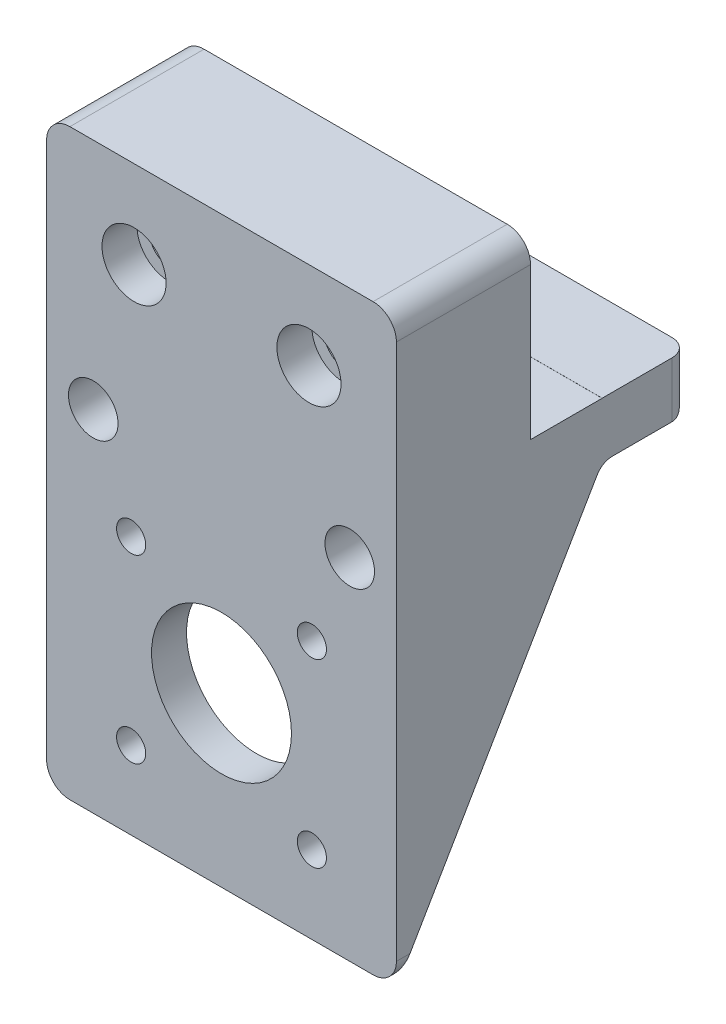
SolidWorks part; units mm, degrees
ref_plane "Front Plane" through (0, 0, 0) normal (0, 0, 1) x (1, 0, 0)
ref_plane "Top Plane" through (0, 0, 0) normal (0, 1, 0) x (1, 0, 0)
ref_plane "Right Plane" through (0, 0, 0) normal (1, 0, 0) x (0, 0, -1)
ref_plane "Plano1" through (0, 0, 29.3) normal (0, 0, 1) x (1, 0, 0)
sketch "Esboço1" plane through (0, 0, 29.3) normal (0, 0, 1) x (1, 0, 0)
  line L0 (-219.9808, -83.15) -> (-219.9808, -59.15) construction
  line L1 (-219.9808, -100) -> (-219.9808, 0) construction
  line L7 (-245.9808, -100) -> (-193.9808, -100)
  line L8 (-249.9808, -96) -> (-249.9808, -4)
  line L9 (-245.9808, 0) -> (-193.9808, 0)
  line L10 (-189.9808, -96) -> (-189.9808, -4)
  arc A0 (-193.9808, 0) -> (-189.9808, -4) centre (-193.9808, -4) cw
  arc A1 (-249.9808, -4) -> (-245.9808, 0) centre (-245.9808, -4) cw
  circle A3 centre (-219.9808, -71.15) radius 12
  arc A4 (-193.9808, -100) -> (-189.9808, -96) centre (-193.9808, -96) ccw
  circle A6 centre (-235.4808, -86.65) radius 2.5
  arc A7 (-245.9808, -100) -> (-249.9808, -96) centre (-245.9808, -96) cw
  circle A9 centre (-235.4808, -55.65) radius 2.5
  circle A12 centre (-204.4808, -86.65) radius 2.5
  circle A15 centre (-204.4808, -55.65) radius 2.5
  point P28 (-189.9808, 0)
  point P31 (-249.9808, 0)
  point P36 (-249.9808, -100)
  dimension "D8" = 4
  dimension "D6" = 100
  dimension "D7" = 60
extrude "Ressalto-extrusão1" add sketch "Esboço1" along normal blind 6
sketch "Esboço2" plane through (0, 0, 29.3) normal (0, 0, -1) x (-1, 0, 0)
  line L8 (189.9808, -4) -> (189.9808, -96)
  line L9 (193.9808, -100) -> (245.9808, -100)
  line L10 (249.9808, -96) -> (249.9808, -4)
  line L11 (245.9808, 0) -> (193.9808, 0)
  line L12 (189.9808, -4) -> (189.9808, -96)
  line L13 (193.9808, -100) -> (245.9808, -100)
  line L14 (249.9808, -96) -> (249.9808, -4)
  line L15 (245.9808, 0) -> (193.9808, 0)
  line L28 (237.9592, -48) -> (202.0024, -48)
  line L29 (202.0024, -48) -> (196.8308, -53.1716)
  line L30 (196.8308, -53.1716) -> (196.8308, -89.1284)
  line L31 (196.8308, -89.1284) -> (202.0024, -94.3)
  line L32 (202.0024, -94.3) -> (237.9592, -94.3)
  line L33 (237.9592, -94.3) -> (243.1308, -89.1284)
  line L34 (243.1308, -89.1284) -> (243.1308, -53.1716)
  line L35 (243.1308, -53.1716) -> (237.9592, -48)
  line L36 (237.9592, -48) -> (202.0024, -48)
  line L37 (202.0024, -48) -> (196.8308, -53.1716)
  line L38 (196.8308, -53.1716) -> (196.8308, -89.1284)
  line L39 (196.8308, -89.1284) -> (202.0024, -94.3)
  line L40 (202.0024, -94.3) -> (237.9592, -94.3)
  line L41 (237.9592, -94.3) -> (243.1308, -89.1284)
  line L42 (243.1308, -89.1284) -> (243.1308, -53.1716)
  line L43 (243.1308, -53.1716) -> (237.9592, -48)
  arc A8 (193.9808, 0) -> (189.9808, -4) centre (193.9808, -4) ccw
  arc A9 (189.9808, -96) -> (193.9808, -100) centre (193.9808, -96) ccw
  arc A10 (245.9808, -100) -> (249.9808, -96) centre (245.9808, -96) ccw
  arc A11 (249.9808, -4) -> (245.9808, 0) centre (245.9808, -4) ccw
  arc A12 (193.9808, 0) -> (189.9808, -4) centre (193.9808, -4) ccw
  arc A13 (189.9808, -96) -> (193.9808, -100) centre (193.9808, -96) ccw
  arc A14 (245.9808, -100) -> (249.9808, -96) centre (245.9808, -96) ccw
  arc A15 (249.9808, -4) -> (245.9808, 0) centre (245.9808, -4) ccw
  dimension "D1" = 0
  dimension "D2" = 3
extrude "Ressalto-extrusão2" add sketch "Esboço2" along normal blind 50
sketch "Esboço3" plane through (-249.9808, 0, 0) normal (-1, 0, 0) x (0, 0, 1)
  line L2 (35.3, -100) -> (-20.7, -100)
  line L3 (35.3, -100) -> (-20.7, -100)
  line L20 (35.3, -100) -> (0, -39.4857)
  line L21 (-20.7, -31.0564) -> (-20.7, -100)
  line L22 (0, -39.4857) -> (0, -31.0564)
  line L26 (0, -31.0564) -> (-20.7, -31.0564)
  dimension "D1" = 0
extrude "Corte-extrusão1" cut sketch "Esboço3" against normal through all
sketch "Esboço4" plane through (0, 0, 0) normal (0, 0, -1) x (-1, 0, 0)
  line L1 (189.9808, -39.4857) -> (249.9808, -39.4857)
  line L2 (189.9808, -39.4857) -> (189.9808, -29.9857)
  line L3 (189.9808, -29.9857) -> (249.9808, -29.9857)
  line L4 (249.9808, -39.4857) -> (249.9808, -29.9857)
  dimension "D1" = 9.5
sketch "Esboço5" plane through (0, 0, 35.3) normal (0, 0, 1) x (1, 0, 0)
  line L0 (-262.6292, -30) -> (-149.7916, -30) construction
  line L1 (-427.912, -30) -> (12.088, -30) construction
  line L2 (-219.9808, 0) -> (-219.9808, -100) construction
  line L3 (-193.9808, 0) -> (-245.9808, 0) construction
  line L4 (-245.9808, -100) -> (-193.9808, -100) construction
  circle A0 centre (-241.9808, -40) radius 4.25
  circle A1 centre (-197.9808, -40) radius 4.25
  dimension "D1" = 8.5
  dimension "D2" = 22
  dimension "D3" = 10
extrude "Corte-extrusão2" cut sketch "Esboço5" against normal blind 15
hole_wizard "Rebaixo para SHCS M61" positions "Esboço7" profile "Esboço6" counterbore size "M6" standard "Ansi Metric" end condition through all
sketch "Esboço7" plane through (0, 0, 35.3) normal (0, 0, 1) x (1, 0, 0)
  line L0 (-219.9808, 0) -> (-219.9808, -100) construction
  line L1 (-193.9808, 0) -> (-245.9808, 0) construction
  line L2 (-245.9808, -100) -> (-193.9808, -100) construction
  point P8 (-204.9808, -15)
  point P11 (-234.9808, -15)
  dimension "D1" = 15
  dimension "D2" = 15
  dimension "D3" = 15
  dimension "D4" = 15
sketch "Esboço6" plane through (-234.9808, -15, 35.3) normal (1, 0, 0) x (0, -1, 0)
  line L0 (0, 0) -> (0, 56)
  line L1 (0, 56) -> (3.3, 56)
  line L3 (3.3, 56) -> (3.3, 6)
  line L4 (3.3, 6) -> (5.5, 6)
  line L5 (5.5, 6) -> (5.5, 0)
  line L7 (5.5, 0) -> (0, 0)
  line L11 (0, -6.35) -> (0, 107.95) construction
  dimension "Thru Hole Dia." = 6.6
  dimension "Thru Hole Depth" = 56
  dimension "C'Bore Dia." = 11
  dimension "C'Bore Depth" = 6
sketch "Esboço10" plane through (-249.9808, 0, 0) normal (-1, 0, 0) x (0, 0, 1)
  line L0 (-17.7, -15) -> (12.2826, -15) construction
  line L1 (12.2913, 0) -> (-27.7087, 0)
  line L2 (12.2913, 0) -> (12.2913, -30)
  line L3 (12.2913, -30) -> (0, -30)
  line L4 (-27.7087, 0) -> (-27.7087, -30)
  line L6 (12.2826, -30) -> (12.2826, 0) construction
  line L10 (12.2913, -15) -> (-17.7087, -15) construction
  line L11 (0, -31.5328) -> (0, -30)
  line L12 (0, -39.4857) -> (0, -31.0564) construction
  line L13 (0, -31.5328) -> (-21.2353, -31.5328)
  line L14 (-21.2353, -31.5328) -> (-21.2353, -30)
  line L15 (-21.2353, -30) -> (-27.7087, -30)
  point P10 (-2.7087, -15)
  point P11 (-2.7087, -15)
  dimension "D1" = 30
  dimension "D2" = 40
extrude "Corte-extrusão3" cut sketch "Esboço10" against normal through all
extrude "Ressalto-extrusão3" add sketch "Esboço4" along normal blind 15
fillet "Filete1" radius 3 4 edges at (-219.9808, -39.4857, 0) (-249.9808, -34.7357, -15) (-189.9808, -34.7357, -15) (-219.9808, -39.4857, -15)
